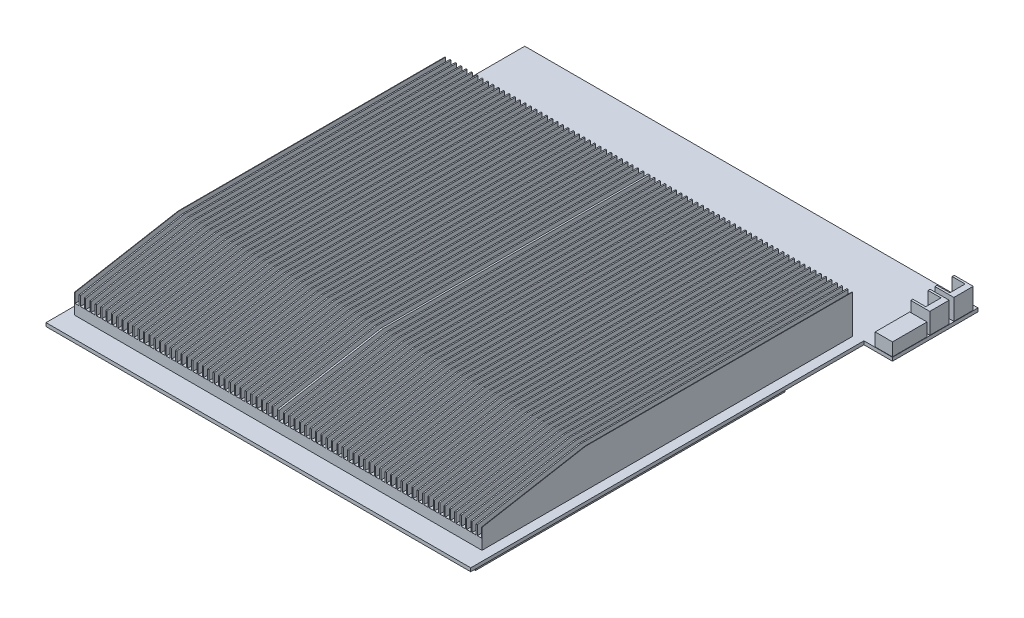
SolidWorks part; units mm, degrees
ref_plane "Front Plane" through (0, 0, 0) normal (0, 0, 1) x (1, 0, 0)
ref_plane "Top Plane" through (0, 0, 0) normal (0, 1, 0) x (1, 0, 0)
ref_plane "Right Plane" through (0, 0, 0) normal (1, 0, 0) x (0, 0, -1)
sketch "Sketch1" plane through (0, 0, 0) normal (0, 1, 0) x (1, 0, 0)
  line L0 (0, 0) -> (0, 277)
  line L1 (0, 277) -> (262.25, 277)
  line L2 (262.25, 277) -> (262.25, 227.5)
  line L3 (262.25, 227.5) -> (245.75, 227.5)
  line L4 (245.75, 227.5) -> (245.75, 0)
  line L5 (245.75, 0) -> (0, 0)
  dimension "D1" = 277
  dimension "D2" = 245.75
  dimension "D3" = 49.5
  dimension "D4" = 16.5
extrude "Boss-Extrude1" add sketch "Sketch1" along normal blind 2
sketch "Sketch2" plane through (0, 2, 0) normal (0, 1, 0) x (1, 0, 0)
  line L0 (245.75, 0) -> (245.75, 227.5) construction
  line L1 (4.5, 226.5) -> (240.25, 226.5)
  line L2 (4.5, 226.5) -> (4.5, 12)
  line L3 (4.5, 12) -> (240.25, 12)
  line L4 (240.25, 226.5) -> (240.25, 12)
  line L5 (4.5, 226.5) -> (240.25, 12) construction
  line L6 (4.5, 12) -> (240.25, 226.5) construction
  line L7 (0, 0) -> (245.75, 0) construction
  line L8 (0, 277) -> (0, 0) construction
  line L9 (262.25, 277) -> (0, 277) construction
  point P4 (122.375, 119.25)
  dimension "D1" = 5.5
  dimension "D2" = 12
  dimension "D3" = 4.5
  dimension "D4" = 50.5
extrude "Boss-Extrude2" add sketch "Sketch2" along normal blind 22.2
sketch "Sketch3" plane through (240.25, 0, 0) normal (1, 0, 0) x (0, 0, -1)
  line L0 (12, 13.5) -> (72, 24.2)
  line L1 (12, 24.2) -> (12, 2) construction
  line L2 (12, 24.2) -> (226.5, 24.2) construction
  line L3 (72, 24.2) -> (12, 24.2)
  line L4 (12, 24.2) -> (12, 13.5)
  dimension "D1" = 60
  dimension "D2" = 10.7
extrude "Cut-Extrude1" cut sketch "Sketch3" against normal up to surface (235.75 mm away) up to face at (4.5, 13.1, -119.25)
sketch "Sketch5" plane through (0, 0, 0) normal (0, -1, 0) x (1, 0, 0)
  line L0 (7.9691, -193.75) -> (7.9691, -14.75)
  line L6 (233.7585, -14.75) -> (233.7585, -193.75)
  line L9 (7.9691, -193.75) -> (67.4691, -193.75)
  line L10 (67.4691, -193.75) -> (67.4691, -226.5)
  line L11 (67.4691, -226.5) -> (174.2585, -226.5)
  line L12 (174.2585, -226.5) -> (174.2585, -193.75)
  line L13 (174.2585, -193.75) -> (233.7585, -193.75)
  line L14 (233.7585, -14.75) -> (7.9691, -14.75)
  line L15 (0, 0) -> (245.75, 0) construction
  line L16 (262.25, -277) -> (0, -277) construction
  line L18 (122.5508, -241.25) -> (149.8508, -241.25)
  line L19 (122.5508, -241.25) -> (122.5508, -271.5)
  line L20 (122.5508, -271.5) -> (149.8508, -271.5)
  line L21 (149.8508, -241.25) -> (149.8508, -271.5)
  line L22 (122.5508, -241.25) -> (149.8508, -271.5) construction
  line L23 (122.5508, -271.5) -> (149.8508, -241.25) construction
  point P16 (136.2008, -256.375)
  dimension "D1" = 14.75
  dimension "D2" = 50.5
  dimension "D3" = 83.25
  dimension "D4" = 59.5
  dimension "D5" = 5.5
  dimension "D6" = 14.75
  dimension "D7" = 27.3
extrude "Boss-Extrude4" add sketch "Sketch5" along normal blind 12.75
sketch "Sketch6" plane through (0, 0, -226.5) normal (0, 0, -1) x (-1, 0, 0)
  line L0 (-122.375, 24.2) -> (-122.375, 2) construction
  line L1 (-240.25, 24.2) -> (-4.5, 24.2) construction
  line L2 (-240.25, 2) -> (-4.5, 2) construction
  line L3 (-262.25, 2) -> (0, 2) construction
  line L4 (-122.875, 24.2) -> (-125.275, 24.2)
  line L5 (-122.875, 24.2) -> (-122.875, 8)
  line L6 (-122.875, 8) -> (-125.275, 8)
  line L7 (-125.275, 24.2) -> (-125.275, 8)
  line L8 (-122.875, 24.2) -> (-125.275, 8) construction
  line L9 (-122.875, 8) -> (-125.275, 24.2) construction
  line L10 (-121.875, 8) -> (-119.475, 24.2) construction
  line L11 (-121.875, 24.2) -> (-119.475, 8) construction
  line L12 (-119.475, 24.2) -> (-119.475, 8)
  line L13 (-121.875, 8) -> (-119.475, 8)
  line L14 (-121.875, 24.2) -> (-121.875, 8)
  line L15 (-121.875, 24.2) -> (-119.475, 24.2)
  line L16 (-125.975, 24.2) -> (-128.375, 24.2)
  line L17 (-125.975, 24.2) -> (-125.975, 8)
  line L18 (-125.975, 8) -> (-128.375, 8)
  line L19 (-128.375, 24.2) -> (-128.375, 8)
  line L20 (-125.975, 24.2) -> (-128.375, 8) construction
  line L21 (-125.975, 8) -> (-128.375, 24.2) construction
  line L22 (-129.075, 24.2) -> (-131.475, 24.2)
  line L23 (-129.075, 24.2) -> (-129.075, 8)
  line L24 (-129.075, 8) -> (-131.475, 8)
  line L25 (-131.475, 24.2) -> (-131.475, 8)
  line L26 (-129.075, 24.2) -> (-131.475, 8) construction
  line L27 (-129.075, 8) -> (-131.475, 24.2) construction
  line L28 (-132.175, 24.2) -> (-134.575, 24.2)
  line L29 (-132.175, 24.2) -> (-132.175, 8)
  line L30 (-132.175, 8) -> (-134.575, 8)
  line L31 (-134.575, 24.2) -> (-134.575, 8)
  line L32 (-132.175, 24.2) -> (-134.575, 8) construction
  line L33 (-132.175, 8) -> (-134.575, 24.2) construction
  line L34 (-135.275, 24.2) -> (-137.675, 24.2)
  line L35 (-135.275, 24.2) -> (-135.275, 8)
  line L36 (-135.275, 8) -> (-137.675, 8)
  line L37 (-137.675, 24.2) -> (-137.675, 8)
  line L38 (-135.275, 24.2) -> (-137.675, 8) construction
  line L39 (-135.275, 8) -> (-137.675, 24.2) construction
  line L40 (-138.375, 24.2) -> (-140.775, 24.2)
  line L41 (-138.375, 24.2) -> (-138.375, 8)
  line L42 (-138.375, 8) -> (-140.775, 8)
  line L43 (-140.775, 24.2) -> (-140.775, 8)
  line L44 (-138.375, 24.2) -> (-140.775, 8) construction
  line L45 (-138.375, 8) -> (-140.775, 24.2) construction
  line L46 (-141.475, 24.2) -> (-143.875, 24.2)
  line L47 (-141.475, 24.2) -> (-141.475, 8)
  line L48 (-141.475, 8) -> (-143.875, 8)
  line L49 (-143.875, 24.2) -> (-143.875, 8)
  line L50 (-141.475, 24.2) -> (-143.875, 8) construction
  line L51 (-141.475, 8) -> (-143.875, 24.2) construction
  line L52 (-144.575, 24.2) -> (-146.975, 24.2)
  line L53 (-144.575, 24.2) -> (-144.575, 8)
  line L54 (-144.575, 8) -> (-146.975, 8)
  line L55 (-146.975, 24.2) -> (-146.975, 8)
  line L56 (-144.575, 24.2) -> (-146.975, 8) construction
  line L57 (-144.575, 8) -> (-146.975, 24.2) construction
  line L58 (-147.675, 24.2) -> (-150.075, 24.2)
  line L59 (-147.675, 24.2) -> (-147.675, 8)
  line L60 (-147.675, 8) -> (-150.075, 8)
  line L61 (-150.075, 24.2) -> (-150.075, 8)
  line L62 (-147.675, 24.2) -> (-150.075, 8) construction
  line L63 (-147.675, 8) -> (-150.075, 24.2) construction
  line L64 (-150.775, 24.2) -> (-153.175, 24.2)
  line L65 (-150.775, 24.2) -> (-150.775, 8)
  line L66 (-150.775, 8) -> (-153.175, 8)
  line L67 (-153.175, 24.2) -> (-153.175, 8)
  line L68 (-150.775, 24.2) -> (-153.175, 8) construction
  line L69 (-150.775, 8) -> (-153.175, 24.2) construction
  line L70 (-153.875, 24.2) -> (-156.275, 24.2)
  line L71 (-153.875, 24.2) -> (-153.875, 8)
  line L72 (-153.875, 8) -> (-156.275, 8)
  line L73 (-156.275, 24.2) -> (-156.275, 8)
  line L74 (-153.875, 24.2) -> (-156.275, 8) construction
  line L75 (-153.875, 8) -> (-156.275, 24.2) construction
  line L76 (-156.975, 24.2) -> (-159.375, 24.2)
  line L77 (-156.975, 24.2) -> (-156.975, 8)
  line L78 (-156.975, 8) -> (-159.375, 8)
  line L79 (-159.375, 24.2) -> (-159.375, 8)
  line L80 (-156.975, 24.2) -> (-159.375, 8) construction
  line L81 (-156.975, 8) -> (-159.375, 24.2) construction
  line L82 (-160.075, 24.2) -> (-162.475, 24.2)
  line L83 (-160.075, 24.2) -> (-160.075, 8)
  line L84 (-160.075, 8) -> (-162.475, 8)
  line L85 (-162.475, 24.2) -> (-162.475, 8)
  line L86 (-160.075, 24.2) -> (-162.475, 8) construction
  line L87 (-160.075, 8) -> (-162.475, 24.2) construction
  line L88 (-163.175, 24.2) -> (-165.575, 24.2)
  line L89 (-163.175, 24.2) -> (-163.175, 8)
  line L90 (-163.175, 8) -> (-165.575, 8)
  line L91 (-165.575, 24.2) -> (-165.575, 8)
  line L92 (-163.175, 24.2) -> (-165.575, 8) construction
  line L93 (-163.175, 8) -> (-165.575, 24.2) construction
  line L94 (-166.275, 24.2) -> (-168.675, 24.2)
  line L95 (-166.275, 24.2) -> (-166.275, 8)
  line L96 (-166.275, 8) -> (-168.675, 8)
  line L97 (-168.675, 24.2) -> (-168.675, 8)
  line L98 (-166.275, 24.2) -> (-168.675, 8) construction
  line L99 (-166.275, 8) -> (-168.675, 24.2) construction
  line L100 (-169.375, 24.2) -> (-171.775, 24.2)
  line L101 (-169.375, 24.2) -> (-169.375, 8)
  line L102 (-169.375, 8) -> (-171.775, 8)
  line L103 (-171.775, 24.2) -> (-171.775, 8)
  line L104 (-169.375, 24.2) -> (-171.775, 8) construction
  line L105 (-169.375, 8) -> (-171.775, 24.2) construction
  line L106 (-172.475, 24.2) -> (-174.875, 24.2)
  line L107 (-172.475, 24.2) -> (-172.475, 8)
  line L108 (-172.475, 8) -> (-174.875, 8)
  line L109 (-174.875, 24.2) -> (-174.875, 8)
  line L110 (-172.475, 24.2) -> (-174.875, 8) construction
  line L111 (-172.475, 8) -> (-174.875, 24.2) construction
  line L112 (-175.575, 24.2) -> (-177.975, 24.2)
  line L113 (-175.575, 24.2) -> (-175.575, 8)
  line L114 (-175.575, 8) -> (-177.975, 8)
  line L115 (-177.975, 24.2) -> (-177.975, 8)
  line L116 (-175.575, 24.2) -> (-177.975, 8) construction
  line L117 (-175.575, 8) -> (-177.975, 24.2) construction
  line L118 (-178.675, 24.2) -> (-181.075, 24.2)
  line L119 (-178.675, 24.2) -> (-178.675, 8)
  line L120 (-178.675, 8) -> (-181.075, 8)
  line L121 (-181.075, 24.2) -> (-181.075, 8)
  line L122 (-178.675, 24.2) -> (-181.075, 8) construction
  line L123 (-178.675, 8) -> (-181.075, 24.2) construction
  line L124 (-181.775, 24.2) -> (-184.175, 24.2)
  line L125 (-181.775, 24.2) -> (-181.775, 8)
  line L126 (-181.775, 8) -> (-184.175, 8)
  line L127 (-184.175, 24.2) -> (-184.175, 8)
  line L128 (-181.775, 24.2) -> (-184.175, 8) construction
  line L129 (-181.775, 8) -> (-184.175, 24.2) construction
  line L130 (-184.875, 24.2) -> (-187.275, 24.2)
  line L131 (-184.875, 24.2) -> (-184.875, 8)
  line L132 (-184.875, 8) -> (-187.275, 8)
  line L133 (-187.275, 24.2) -> (-187.275, 8)
  line L134 (-184.875, 24.2) -> (-187.275, 8) construction
  line L135 (-184.875, 8) -> (-187.275, 24.2) construction
  line L136 (-187.975, 24.2) -> (-190.375, 24.2)
  line L137 (-187.975, 24.2) -> (-187.975, 8)
  line L138 (-187.975, 8) -> (-190.375, 8)
  line L139 (-190.375, 24.2) -> (-190.375, 8)
  line L140 (-187.975, 24.2) -> (-190.375, 8) construction
  line L141 (-187.975, 8) -> (-190.375, 24.2) construction
  line L142 (-191.075, 24.2) -> (-193.475, 24.2)
  line L143 (-191.075, 24.2) -> (-191.075, 8)
  line L144 (-191.075, 8) -> (-193.475, 8)
  line L145 (-193.475, 24.2) -> (-193.475, 8)
  line L146 (-191.075, 24.2) -> (-193.475, 8) construction
  line L147 (-191.075, 8) -> (-193.475, 24.2) construction
  line L148 (-194.175, 24.2) -> (-196.575, 24.2)
  line L149 (-194.175, 24.2) -> (-194.175, 8)
  line L150 (-194.175, 8) -> (-196.575, 8)
  line L151 (-196.575, 24.2) -> (-196.575, 8)
  line L152 (-194.175, 24.2) -> (-196.575, 8) construction
  line L153 (-194.175, 8) -> (-196.575, 24.2) construction
  line L154 (-197.275, 24.2) -> (-199.675, 24.2)
  line L155 (-197.275, 24.2) -> (-197.275, 8)
  line L156 (-197.275, 8) -> (-199.675, 8)
  line L157 (-199.675, 24.2) -> (-199.675, 8)
  line L158 (-197.275, 24.2) -> (-199.675, 8) construction
  line L159 (-197.275, 8) -> (-199.675, 24.2) construction
  line L160 (-200.375, 24.2) -> (-202.775, 24.2)
  line L161 (-200.375, 24.2) -> (-200.375, 8)
  line L162 (-200.375, 8) -> (-202.775, 8)
  line L163 (-202.775, 24.2) -> (-202.775, 8)
  line L164 (-200.375, 24.2) -> (-202.775, 8) construction
  line L165 (-200.375, 8) -> (-202.775, 24.2) construction
  line L166 (-203.475, 24.2) -> (-205.875, 24.2)
  line L167 (-203.475, 24.2) -> (-203.475, 8)
  line L168 (-203.475, 8) -> (-205.875, 8)
  line L169 (-205.875, 24.2) -> (-205.875, 8)
  line L170 (-203.475, 24.2) -> (-205.875, 8) construction
  line L171 (-203.475, 8) -> (-205.875, 24.2) construction
  line L172 (-206.575, 24.2) -> (-208.975, 24.2)
  line L173 (-206.575, 24.2) -> (-206.575, 8)
  line L174 (-206.575, 8) -> (-208.975, 8)
  line L175 (-208.975, 24.2) -> (-208.975, 8)
  line L176 (-206.575, 24.2) -> (-208.975, 8) construction
  line L177 (-206.575, 8) -> (-208.975, 24.2) construction
  line L178 (-209.675, 24.2) -> (-212.075, 24.2)
  line L179 (-209.675, 24.2) -> (-209.675, 8)
  line L180 (-209.675, 8) -> (-212.075, 8)
  line L181 (-212.075, 24.2) -> (-212.075, 8)
  line L182 (-209.675, 24.2) -> (-212.075, 8) construction
  line L183 (-209.675, 8) -> (-212.075, 24.2) construction
  line L184 (-212.775, 24.2) -> (-215.175, 24.2)
  line L185 (-212.775, 24.2) -> (-212.775, 8)
  line L186 (-212.775, 8) -> (-215.175, 8)
  line L187 (-215.175, 24.2) -> (-215.175, 8)
  line L188 (-212.775, 24.2) -> (-215.175, 8) construction
  line L189 (-212.775, 8) -> (-215.175, 24.2) construction
  line L190 (-215.875, 24.2) -> (-218.275, 24.2)
  line L191 (-215.875, 24.2) -> (-215.875, 8)
  line L192 (-215.875, 8) -> (-218.275, 8)
  line L193 (-218.275, 24.2) -> (-218.275, 8)
  line L194 (-215.875, 24.2) -> (-218.275, 8) construction
  line L195 (-215.875, 8) -> (-218.275, 24.2) construction
  line L196 (-218.975, 24.2) -> (-221.375, 24.2)
  line L197 (-218.975, 24.2) -> (-218.975, 8)
  line L198 (-218.975, 8) -> (-221.375, 8)
  line L199 (-221.375, 24.2) -> (-221.375, 8)
  line L200 (-218.975, 24.2) -> (-221.375, 8) construction
  line L201 (-218.975, 8) -> (-221.375, 24.2) construction
  line L202 (-222.075, 24.2) -> (-224.475, 24.2)
  line L203 (-222.075, 24.2) -> (-222.075, 8)
  line L204 (-222.075, 8) -> (-224.475, 8)
  line L205 (-224.475, 24.2) -> (-224.475, 8)
  line L206 (-222.075, 24.2) -> (-224.475, 8) construction
  line L207 (-222.075, 8) -> (-224.475, 24.2) construction
  line L208 (-225.175, 24.2) -> (-227.575, 24.2)
  line L209 (-225.175, 24.2) -> (-225.175, 8)
  line L210 (-225.175, 8) -> (-227.575, 8)
  line L211 (-227.575, 24.2) -> (-227.575, 8)
  line L212 (-225.175, 24.2) -> (-227.575, 8) construction
  line L213 (-225.175, 8) -> (-227.575, 24.2) construction
  line L214 (-228.275, 24.2) -> (-230.675, 24.2)
  line L215 (-228.275, 24.2) -> (-228.275, 8)
  line L216 (-228.275, 8) -> (-230.675, 8)
  line L217 (-230.675, 24.2) -> (-230.675, 8)
  line L218 (-228.275, 24.2) -> (-230.675, 8) construction
  line L219 (-228.275, 8) -> (-230.675, 24.2) construction
  line L220 (-231.375, 24.2) -> (-233.775, 24.2)
  line L221 (-231.375, 24.2) -> (-231.375, 8)
  line L222 (-231.375, 8) -> (-233.775, 8)
  line L223 (-233.775, 24.2) -> (-233.775, 8)
  line L224 (-231.375, 24.2) -> (-233.775, 8) construction
  line L225 (-231.375, 8) -> (-233.775, 24.2) construction
  line L226 (-234.475, 24.2) -> (-236.875, 24.2)
  line L227 (-234.475, 24.2) -> (-234.475, 8)
  line L228 (-234.475, 8) -> (-236.875, 8)
  line L229 (-236.875, 24.2) -> (-236.875, 8)
  line L230 (-234.475, 24.2) -> (-236.875, 8) construction
  line L231 (-234.475, 8) -> (-236.875, 24.2) construction
  line L232 (-237.575, 24.2) -> (-239.975, 24.2)
  line L233 (-237.575, 24.2) -> (-237.575, 8)
  line L234 (-237.575, 8) -> (-239.975, 8)
  line L235 (-239.975, 24.2) -> (-239.975, 8)
  line L236 (-237.575, 24.2) -> (-239.975, 8) construction
  line L237 (-237.575, 8) -> (-239.975, 24.2) construction
  line L238 (-116.375, 24.2) -> (-116.375, 8)
  line L239 (-118.775, 8) -> (-116.375, 8)
  line L240 (-118.775, 24.2) -> (-118.775, 8)
  line L241 (-118.775, 24.2) -> (-116.375, 24.2)
  line L242 (-118.775, 8) -> (-116.375, 24.2) construction
  line L243 (-118.775, 24.2) -> (-116.375, 8) construction
  line L244 (-113.275, 24.2) -> (-113.275, 8)
  line L245 (-115.675, 8) -> (-113.275, 8)
  line L246 (-115.675, 24.2) -> (-115.675, 8)
  line L247 (-115.675, 24.2) -> (-113.275, 24.2)
  line L248 (-115.675, 8) -> (-113.275, 24.2) construction
  line L249 (-115.675, 24.2) -> (-113.275, 8) construction
  line L250 (-110.175, 24.2) -> (-110.175, 8)
  line L251 (-112.575, 8) -> (-110.175, 8)
  line L252 (-112.575, 24.2) -> (-112.575, 8)
  line L253 (-112.575, 24.2) -> (-110.175, 24.2)
  line L254 (-112.575, 8) -> (-110.175, 24.2) construction
  line L255 (-112.575, 24.2) -> (-110.175, 8) construction
  line L256 (-107.075, 24.2) -> (-107.075, 8)
  line L257 (-109.475, 8) -> (-107.075, 8)
  line L258 (-109.475, 24.2) -> (-109.475, 8)
  line L259 (-109.475, 24.2) -> (-107.075, 24.2)
  line L260 (-109.475, 8) -> (-107.075, 24.2) construction
  line L261 (-109.475, 24.2) -> (-107.075, 8) construction
  line L262 (-103.975, 24.2) -> (-103.975, 8)
  line L263 (-106.375, 8) -> (-103.975, 8)
  line L264 (-106.375, 24.2) -> (-106.375, 8)
  line L265 (-106.375, 24.2) -> (-103.975, 24.2)
  line L266 (-106.375, 8) -> (-103.975, 24.2) construction
  line L267 (-106.375, 24.2) -> (-103.975, 8) construction
  line L268 (-100.875, 24.2) -> (-100.875, 8)
  line L269 (-103.275, 8) -> (-100.875, 8)
  line L270 (-103.275, 24.2) -> (-103.275, 8)
  line L271 (-103.275, 24.2) -> (-100.875, 24.2)
  line L272 (-103.275, 8) -> (-100.875, 24.2) construction
  line L273 (-103.275, 24.2) -> (-100.875, 8) construction
  line L274 (-97.775, 24.2) -> (-97.775, 8)
  line L275 (-100.175, 8) -> (-97.775, 8)
  line L276 (-100.175, 24.2) -> (-100.175, 8)
  line L277 (-100.175, 24.2) -> (-97.775, 24.2)
  line L278 (-100.175, 8) -> (-97.775, 24.2) construction
  line L279 (-100.175, 24.2) -> (-97.775, 8) construction
  line L280 (-94.675, 24.2) -> (-94.675, 8)
  line L281 (-97.075, 8) -> (-94.675, 8)
  line L282 (-97.075, 24.2) -> (-97.075, 8)
  line L283 (-97.075, 24.2) -> (-94.675, 24.2)
  line L284 (-97.075, 8) -> (-94.675, 24.2) construction
  line L285 (-97.075, 24.2) -> (-94.675, 8) construction
  line L286 (-91.575, 24.2) -> (-91.575, 8)
  line L287 (-93.975, 8) -> (-91.575, 8)
  line L288 (-93.975, 24.2) -> (-93.975, 8)
  line L289 (-93.975, 24.2) -> (-91.575, 24.2)
  line L290 (-93.975, 8) -> (-91.575, 24.2) construction
  line L291 (-93.975, 24.2) -> (-91.575, 8) construction
  line L292 (-88.475, 24.2) -> (-88.475, 8)
  line L293 (-90.875, 8) -> (-88.475, 8)
  line L294 (-90.875, 24.2) -> (-90.875, 8)
  line L295 (-90.875, 24.2) -> (-88.475, 24.2)
  line L296 (-90.875, 8) -> (-88.475, 24.2) construction
  line L297 (-90.875, 24.2) -> (-88.475, 8) construction
  line L298 (-85.375, 24.2) -> (-85.375, 8)
  line L299 (-87.775, 8) -> (-85.375, 8)
  line L300 (-87.775, 24.2) -> (-87.775, 8)
  line L301 (-87.775, 24.2) -> (-85.375, 24.2)
  line L302 (-87.775, 8) -> (-85.375, 24.2) construction
  line L303 (-87.775, 24.2) -> (-85.375, 8) construction
  line L304 (-82.275, 24.2) -> (-82.275, 8)
  line L305 (-84.675, 8) -> (-82.275, 8)
  line L306 (-84.675, 24.2) -> (-84.675, 8)
  line L307 (-84.675, 24.2) -> (-82.275, 24.2)
  line L308 (-84.675, 8) -> (-82.275, 24.2) construction
  line L309 (-84.675, 24.2) -> (-82.275, 8) construction
  line L310 (-79.175, 24.2) -> (-79.175, 8)
  line L311 (-81.575, 8) -> (-79.175, 8)
  line L312 (-81.575, 24.2) -> (-81.575, 8)
  line L313 (-81.575, 24.2) -> (-79.175, 24.2)
  line L314 (-81.575, 8) -> (-79.175, 24.2) construction
  line L315 (-81.575, 24.2) -> (-79.175, 8) construction
  line L316 (-76.075, 24.2) -> (-76.075, 8)
  line L317 (-78.475, 8) -> (-76.075, 8)
  line L318 (-78.475, 24.2) -> (-78.475, 8)
  line L319 (-78.475, 24.2) -> (-76.075, 24.2)
  line L320 (-78.475, 8) -> (-76.075, 24.2) construction
  line L321 (-78.475, 24.2) -> (-76.075, 8) construction
  line L322 (-72.975, 24.2) -> (-72.975, 8)
  line L323 (-75.375, 8) -> (-72.975, 8)
  line L324 (-75.375, 24.2) -> (-75.375, 8)
  line L325 (-75.375, 24.2) -> (-72.975, 24.2)
  line L326 (-75.375, 8) -> (-72.975, 24.2) construction
  line L327 (-75.375, 24.2) -> (-72.975, 8) construction
  line L328 (-69.875, 24.2) -> (-69.875, 8)
  line L329 (-72.275, 8) -> (-69.875, 8)
  line L330 (-72.275, 24.2) -> (-72.275, 8)
  line L331 (-72.275, 24.2) -> (-69.875, 24.2)
  line L332 (-72.275, 8) -> (-69.875, 24.2) construction
  line L333 (-72.275, 24.2) -> (-69.875, 8) construction
  line L334 (-66.775, 24.2) -> (-66.775, 8)
  line L335 (-69.175, 8) -> (-66.775, 8)
  line L336 (-69.175, 24.2) -> (-69.175, 8)
  line L337 (-69.175, 24.2) -> (-66.775, 24.2)
  line L338 (-69.175, 8) -> (-66.775, 24.2) construction
  line L339 (-69.175, 24.2) -> (-66.775, 8) construction
  line L340 (-63.675, 24.2) -> (-63.675, 8)
  line L341 (-66.075, 8) -> (-63.675, 8)
  line L342 (-66.075, 24.2) -> (-66.075, 8)
  line L343 (-66.075, 24.2) -> (-63.675, 24.2)
  line L344 (-66.075, 8) -> (-63.675, 24.2) construction
  line L345 (-66.075, 24.2) -> (-63.675, 8) construction
  line L346 (-60.575, 24.2) -> (-60.575, 8)
  line L347 (-62.975, 8) -> (-60.575, 8)
  line L348 (-62.975, 24.2) -> (-62.975, 8)
  line L349 (-62.975, 24.2) -> (-60.575, 24.2)
  line L350 (-62.975, 8) -> (-60.575, 24.2) construction
  line L351 (-62.975, 24.2) -> (-60.575, 8) construction
  line L352 (-57.475, 24.2) -> (-57.475, 8)
  line L353 (-59.875, 8) -> (-57.475, 8)
  line L354 (-59.875, 24.2) -> (-59.875, 8)
  line L355 (-59.875, 24.2) -> (-57.475, 24.2)
  line L356 (-59.875, 8) -> (-57.475, 24.2) construction
  line L357 (-59.875, 24.2) -> (-57.475, 8) construction
  line L358 (-54.375, 24.2) -> (-54.375, 8)
  line L359 (-56.775, 8) -> (-54.375, 8)
  line L360 (-56.775, 24.2) -> (-56.775, 8)
  line L361 (-56.775, 24.2) -> (-54.375, 24.2)
  line L362 (-56.775, 8) -> (-54.375, 24.2) construction
  line L363 (-56.775, 24.2) -> (-54.375, 8) construction
  line L364 (-51.275, 24.2) -> (-51.275, 8)
  line L365 (-53.675, 8) -> (-51.275, 8)
  line L366 (-53.675, 24.2) -> (-53.675, 8)
  line L367 (-53.675, 24.2) -> (-51.275, 24.2)
  line L368 (-53.675, 8) -> (-51.275, 24.2) construction
  line L369 (-53.675, 24.2) -> (-51.275, 8) construction
  line L370 (-48.175, 24.2) -> (-48.175, 8)
  line L371 (-50.575, 8) -> (-48.175, 8)
  line L372 (-50.575, 24.2) -> (-50.575, 8)
  line L373 (-50.575, 24.2) -> (-48.175, 24.2)
  line L374 (-50.575, 8) -> (-48.175, 24.2) construction
  line L375 (-50.575, 24.2) -> (-48.175, 8) construction
  line L376 (-45.075, 24.2) -> (-45.075, 8)
  line L377 (-47.475, 8) -> (-45.075, 8)
  line L378 (-47.475, 24.2) -> (-47.475, 8)
  line L379 (-47.475, 24.2) -> (-45.075, 24.2)
  line L380 (-47.475, 8) -> (-45.075, 24.2) construction
  line L381 (-47.475, 24.2) -> (-45.075, 8) construction
  line L382 (-41.975, 24.2) -> (-41.975, 8)
  line L383 (-44.375, 8) -> (-41.975, 8)
  line L384 (-44.375, 24.2) -> (-44.375, 8)
  line L385 (-44.375, 24.2) -> (-41.975, 24.2)
  line L386 (-44.375, 8) -> (-41.975, 24.2) construction
  line L387 (-44.375, 24.2) -> (-41.975, 8) construction
  line L388 (-38.875, 24.2) -> (-38.875, 8)
  line L389 (-41.275, 8) -> (-38.875, 8)
  line L390 (-41.275, 24.2) -> (-41.275, 8)
  line L391 (-41.275, 24.2) -> (-38.875, 24.2)
  line L392 (-41.275, 8) -> (-38.875, 24.2) construction
  line L393 (-41.275, 24.2) -> (-38.875, 8) construction
  line L394 (-35.775, 24.2) -> (-35.775, 8)
  line L395 (-38.175, 8) -> (-35.775, 8)
  line L396 (-38.175, 24.2) -> (-38.175, 8)
  line L397 (-38.175, 24.2) -> (-35.775, 24.2)
  line L398 (-38.175, 8) -> (-35.775, 24.2) construction
  line L399 (-38.175, 24.2) -> (-35.775, 8) construction
  line L400 (-32.675, 24.2) -> (-32.675, 8)
  line L401 (-35.075, 8) -> (-32.675, 8)
  line L402 (-35.075, 24.2) -> (-35.075, 8)
  line L403 (-35.075, 24.2) -> (-32.675, 24.2)
  line L404 (-35.075, 8) -> (-32.675, 24.2) construction
  line L405 (-35.075, 24.2) -> (-32.675, 8) construction
  line L406 (-29.575, 24.2) -> (-29.575, 8)
  line L407 (-31.975, 8) -> (-29.575, 8)
  line L408 (-31.975, 24.2) -> (-31.975, 8)
  line L409 (-31.975, 24.2) -> (-29.575, 24.2)
  line L410 (-31.975, 8) -> (-29.575, 24.2) construction
  line L411 (-31.975, 24.2) -> (-29.575, 8) construction
  line L412 (-26.475, 24.2) -> (-26.475, 8)
  line L413 (-28.875, 8) -> (-26.475, 8)
  line L414 (-28.875, 24.2) -> (-28.875, 8)
  line L415 (-28.875, 24.2) -> (-26.475, 24.2)
  line L416 (-28.875, 8) -> (-26.475, 24.2) construction
  line L417 (-28.875, 24.2) -> (-26.475, 8) construction
  line L418 (-23.375, 24.2) -> (-23.375, 8)
  line L419 (-25.775, 8) -> (-23.375, 8)
  line L420 (-25.775, 24.2) -> (-25.775, 8)
  line L421 (-25.775, 24.2) -> (-23.375, 24.2)
  line L422 (-25.775, 8) -> (-23.375, 24.2) construction
  line L423 (-25.775, 24.2) -> (-23.375, 8) construction
  line L424 (-20.275, 24.2) -> (-20.275, 8)
  line L425 (-22.675, 8) -> (-20.275, 8)
  line L426 (-22.675, 24.2) -> (-22.675, 8)
  line L427 (-22.675, 24.2) -> (-20.275, 24.2)
  line L428 (-22.675, 8) -> (-20.275, 24.2) construction
  line L429 (-22.675, 24.2) -> (-20.275, 8) construction
  line L430 (-17.175, 24.2) -> (-17.175, 8)
  line L431 (-19.575, 8) -> (-17.175, 8)
  line L432 (-19.575, 24.2) -> (-19.575, 8)
  line L433 (-19.575, 24.2) -> (-17.175, 24.2)
  line L434 (-19.575, 8) -> (-17.175, 24.2) construction
  line L435 (-19.575, 24.2) -> (-17.175, 8) construction
  line L436 (-14.075, 24.2) -> (-14.075, 8)
  line L437 (-16.475, 8) -> (-14.075, 8)
  line L438 (-16.475, 24.2) -> (-16.475, 8)
  line L439 (-16.475, 24.2) -> (-14.075, 24.2)
  line L440 (-16.475, 8) -> (-14.075, 24.2) construction
  line L441 (-16.475, 24.2) -> (-14.075, 8) construction
  line L442 (-10.975, 24.2) -> (-10.975, 8)
  line L443 (-13.375, 8) -> (-10.975, 8)
  line L444 (-13.375, 24.2) -> (-13.375, 8)
  line L445 (-13.375, 24.2) -> (-10.975, 24.2)
  line L446 (-13.375, 8) -> (-10.975, 24.2) construction
  line L447 (-13.375, 24.2) -> (-10.975, 8) construction
  line L448 (-7.875, 24.2) -> (-7.875, 8)
  line L449 (-10.275, 8) -> (-7.875, 8)
  line L450 (-10.275, 24.2) -> (-10.275, 8)
  line L451 (-10.275, 24.2) -> (-7.875, 24.2)
  line L452 (-10.275, 8) -> (-7.875, 24.2) construction
  line L453 (-10.275, 24.2) -> (-7.875, 8) construction
  line L454 (-4.775, 24.2) -> (-4.775, 8)
  line L455 (-7.175, 8) -> (-4.775, 8)
  line L456 (-7.175, 24.2) -> (-7.175, 8)
  line L457 (-7.175, 24.2) -> (-4.775, 24.2)
  line L458 (-7.175, 8) -> (-4.775, 24.2) construction
  line L459 (-7.175, 24.2) -> (-4.775, 8) construction
  point P10 (-124.075, 16.1)
  point P17 (-120.675, 16.1)
  point P23 (-127.175, 16.1)
  point P28 (-130.275, 16.1)
  point P33 (-133.375, 16.1)
  point P38 (-136.475, 16.1)
  point P43 (-139.575, 16.1)
  point P48 (-142.675, 16.1)
  point P53 (-145.775, 16.1)
  point P58 (-148.875, 16.1)
  point P63 (-151.975, 16.1)
  point P68 (-155.075, 16.1)
  point P73 (-158.175, 16.1)
  point P78 (-161.275, 16.1)
  point P83 (-164.375, 16.1)
  point P88 (-167.475, 16.1)
  point P93 (-170.575, 16.1)
  point P98 (-173.675, 16.1)
  point P103 (-176.775, 16.1)
  point P108 (-179.875, 16.1)
  point P113 (-182.975, 16.1)
  point P118 (-186.075, 16.1)
  point P123 (-189.175, 16.1)
  point P128 (-192.275, 16.1)
  point P133 (-195.375, 16.1)
  point P138 (-198.475, 16.1)
  point P143 (-201.575, 16.1)
  point P148 (-204.675, 16.1)
  point P153 (-207.775, 16.1)
  point P158 (-210.875, 16.1)
  point P163 (-213.975, 16.1)
  point P168 (-217.075, 16.1)
  point P173 (-220.175, 16.1)
  point P178 (-223.275, 16.1)
  point P183 (-226.375, 16.1)
  point P188 (-229.475, 16.1)
  point P193 (-232.575, 16.1)
  point P198 (-235.675, 16.1)
  point P203 (-238.775, 16.1)
  point P209 (-117.575, 16.1)
  point P214 (-114.475, 16.1)
  point P219 (-111.375, 16.1)
  point P224 (-108.275, 16.1)
  point P229 (-105.175, 16.1)
  point P234 (-102.075, 16.1)
  point P239 (-98.975, 16.1)
  point P244 (-95.875, 16.1)
  point P249 (-92.775, 16.1)
  point P254 (-89.675, 16.1)
  point P259 (-86.575, 16.1)
  point P264 (-83.475, 16.1)
  point P269 (-80.375, 16.1)
  point P274 (-77.275, 16.1)
  point P279 (-74.175, 16.1)
  point P284 (-71.075, 16.1)
  point P289 (-67.975, 16.1)
  point P294 (-64.875, 16.1)
  point P299 (-61.775, 16.1)
  point P304 (-58.675, 16.1)
  point P309 (-55.575, 16.1)
  point P314 (-52.475, 16.1)
  point P319 (-49.375, 16.1)
  point P324 (-46.275, 16.1)
  point P329 (-43.175, 16.1)
  point P334 (-40.075, 16.1)
  point P339 (-36.975, 16.1)
  point P344 (-33.875, 16.1)
  point P349 (-30.775, 16.1)
  point P354 (-27.675, 16.1)
  point P359 (-24.575, 16.1)
  point P364 (-21.475, 16.1)
  point P369 (-18.375, 16.1)
  point P374 (-15.275, 16.1)
  point P379 (-12.175, 16.1)
  point P384 (-9.075, 16.1)
  point P389 (-5.975, 16.1)
  dimension "D1" = 1
  dimension "D2" = 6
  dimension "D3" = 2.4
  dimension "D4" = 38
  dimension "D5" = 38
extrude "Cut-Extrude2" cut sketch "Sketch6" against normal through all
sketch "Sketch7" plane through (0, 0, -14.75) normal (0, 0, 1) x (1, 0, 0)
  line L0 (120.8638, 0) -> (120.8638, -12.75) construction
  line L1 (233.7585, 0) -> (7.9691, 0) construction
  line L2 (233.7585, -12.75) -> (7.9691, -12.75) construction
  line L3 (121.8638, -1.9399) -> (124.2638, -12.75) construction
  line L4 (119.8638, -12.75) -> (117.4638, -12.75)
  line L5 (119.8638, -12.75) -> (119.8638, -1.9399)
  line L6 (119.8638, -1.9399) -> (117.4638, -1.9399)
  line L7 (117.4638, -12.75) -> (117.4638, -1.9399)
  line L8 (119.8638, -12.75) -> (117.4638, -1.9399) construction
  line L9 (119.8638, -1.9399) -> (117.4638, -12.75) construction
  line L10 (121.8638, -12.75) -> (124.2638, -1.9399) construction
  line L11 (124.2638, -12.75) -> (124.2638, -1.9399)
  line L12 (121.8638, -1.9399) -> (124.2638, -1.9399)
  line L13 (121.8638, -12.75) -> (121.8638, -1.9399)
  line L14 (121.8638, -12.75) -> (124.2638, -12.75)
  line L15 (127.3638, -12.75) -> (127.3638, -1.9399)
  line L16 (124.9638, -1.9399) -> (127.3638, -1.9399)
  line L17 (124.9638, -12.75) -> (124.9638, -1.9399)
  line L18 (124.9638, -12.75) -> (127.3638, -12.75)
  line L19 (124.9638, -1.9399) -> (127.3638, -12.75) construction
  line L20 (124.9638, -12.75) -> (127.3638, -1.9399) construction
  line L21 (130.4638, -12.75) -> (130.4638, -1.9399)
  line L22 (128.0638, -1.9399) -> (130.4638, -1.9399)
  line L23 (128.0638, -12.75) -> (128.0638, -1.9399)
  line L24 (128.0638, -12.75) -> (130.4638, -12.75)
  line L25 (128.0638, -1.9399) -> (130.4638, -12.75) construction
  line L26 (128.0638, -12.75) -> (130.4638, -1.9399) construction
  line L27 (133.5638, -12.75) -> (133.5638, -1.9399)
  line L28 (131.1638, -1.9399) -> (133.5638, -1.9399)
  line L29 (131.1638, -12.75) -> (131.1638, -1.9399)
  line L30 (131.1638, -12.75) -> (133.5638, -12.75)
  line L31 (131.1638, -1.9399) -> (133.5638, -12.75) construction
  line L32 (131.1638, -12.75) -> (133.5638, -1.9399) construction
  line L33 (136.6638, -12.75) -> (136.6638, -1.9399)
  line L34 (134.2638, -1.9399) -> (136.6638, -1.9399)
  line L35 (134.2638, -12.75) -> (134.2638, -1.9399)
  line L36 (134.2638, -12.75) -> (136.6638, -12.75)
  line L37 (134.2638, -1.9399) -> (136.6638, -12.75) construction
  line L38 (134.2638, -12.75) -> (136.6638, -1.9399) construction
  line L39 (139.7638, -12.75) -> (139.7638, -1.9399)
  line L40 (137.3638, -1.9399) -> (139.7638, -1.9399)
  line L41 (137.3638, -12.75) -> (137.3638, -1.9399)
  line L42 (137.3638, -12.75) -> (139.7638, -12.75)
  line L43 (137.3638, -1.9399) -> (139.7638, -12.75) construction
  line L44 (137.3638, -12.75) -> (139.7638, -1.9399) construction
  line L45 (142.8638, -12.75) -> (142.8638, -1.9399)
  line L46 (140.4638, -1.9399) -> (142.8638, -1.9399)
  line L47 (140.4638, -12.75) -> (140.4638, -1.9399)
  line L48 (140.4638, -12.75) -> (142.8638, -12.75)
  line L49 (140.4638, -1.9399) -> (142.8638, -12.75) construction
  line L50 (140.4638, -12.75) -> (142.8638, -1.9399) construction
  line L51 (145.9638, -12.75) -> (145.9638, -1.9399)
  line L52 (143.5638, -1.9399) -> (145.9638, -1.9399)
  line L53 (143.5638, -12.75) -> (143.5638, -1.9399)
  line L54 (143.5638, -12.75) -> (145.9638, -12.75)
  line L55 (143.5638, -1.9399) -> (145.9638, -12.75) construction
  line L56 (143.5638, -12.75) -> (145.9638, -1.9399) construction
  line L57 (149.0638, -12.75) -> (149.0638, -1.9399)
  line L58 (146.6638, -1.9399) -> (149.0638, -1.9399)
  line L59 (146.6638, -12.75) -> (146.6638, -1.9399)
  line L60 (146.6638, -12.75) -> (149.0638, -12.75)
  line L61 (146.6638, -1.9399) -> (149.0638, -12.75) construction
  line L62 (146.6638, -12.75) -> (149.0638, -1.9399) construction
  line L63 (152.1638, -12.75) -> (152.1638, -1.9399)
  line L64 (149.7638, -1.9399) -> (152.1638, -1.9399)
  line L65 (149.7638, -12.75) -> (149.7638, -1.9399)
  line L66 (149.7638, -12.75) -> (152.1638, -12.75)
  line L67 (149.7638, -1.9399) -> (152.1638, -12.75) construction
  line L68 (149.7638, -12.75) -> (152.1638, -1.9399) construction
  line L69 (155.2638, -12.75) -> (155.2638, -1.9399)
  line L70 (152.8638, -1.9399) -> (155.2638, -1.9399)
  line L71 (152.8638, -12.75) -> (152.8638, -1.9399)
  line L72 (152.8638, -12.75) -> (155.2638, -12.75)
  line L73 (152.8638, -1.9399) -> (155.2638, -12.75) construction
  line L74 (152.8638, -12.75) -> (155.2638, -1.9399) construction
  line L75 (158.3638, -12.75) -> (158.3638, -1.9399)
  line L76 (155.9638, -1.9399) -> (158.3638, -1.9399)
  line L77 (155.9638, -12.75) -> (155.9638, -1.9399)
  line L78 (155.9638, -12.75) -> (158.3638, -12.75)
  line L79 (155.9638, -1.9399) -> (158.3638, -12.75) construction
  line L80 (155.9638, -12.75) -> (158.3638, -1.9399) construction
  line L81 (161.4638, -12.75) -> (161.4638, -1.9399)
  line L82 (159.0638, -1.9399) -> (161.4638, -1.9399)
  line L83 (159.0638, -12.75) -> (159.0638, -1.9399)
  line L84 (159.0638, -12.75) -> (161.4638, -12.75)
  line L85 (159.0638, -1.9399) -> (161.4638, -12.75) construction
  line L86 (159.0638, -12.75) -> (161.4638, -1.9399) construction
  line L87 (164.5638, -12.75) -> (164.5638, -1.9399)
  line L88 (162.1638, -1.9399) -> (164.5638, -1.9399)
  line L89 (162.1638, -12.75) -> (162.1638, -1.9399)
  line L90 (162.1638, -12.75) -> (164.5638, -12.75)
  line L91 (162.1638, -1.9399) -> (164.5638, -12.75) construction
  line L92 (162.1638, -12.75) -> (164.5638, -1.9399) construction
  line L93 (167.6638, -12.75) -> (167.6638, -1.9399)
  line L94 (165.2638, -1.9399) -> (167.6638, -1.9399)
  line L95 (165.2638, -12.75) -> (165.2638, -1.9399)
  line L96 (165.2638, -12.75) -> (167.6638, -12.75)
  line L97 (165.2638, -1.9399) -> (167.6638, -12.75) construction
  line L98 (165.2638, -12.75) -> (167.6638, -1.9399) construction
  line L99 (170.7638, -12.75) -> (170.7638, -1.9399)
  line L100 (168.3638, -1.9399) -> (170.7638, -1.9399)
  line L101 (168.3638, -12.75) -> (168.3638, -1.9399)
  line L102 (168.3638, -12.75) -> (170.7638, -12.75)
  line L103 (168.3638, -1.9399) -> (170.7638, -12.75) construction
  line L104 (168.3638, -12.75) -> (170.7638, -1.9399) construction
  line L105 (173.8638, -12.75) -> (173.8638, -1.9399)
  line L106 (171.4638, -1.9399) -> (173.8638, -1.9399)
  line L107 (171.4638, -12.75) -> (171.4638, -1.9399)
  line L108 (171.4638, -12.75) -> (173.8638, -12.75)
  line L109 (171.4638, -1.9399) -> (173.8638, -12.75) construction
  line L110 (171.4638, -12.75) -> (173.8638, -1.9399) construction
  line L111 (176.9638, -12.75) -> (176.9638, -1.9399)
  line L112 (174.5638, -1.9399) -> (176.9638, -1.9399)
  line L113 (174.5638, -12.75) -> (174.5638, -1.9399)
  line L114 (174.5638, -12.75) -> (176.9638, -12.75)
  line L115 (174.5638, -1.9399) -> (176.9638, -12.75) construction
  line L116 (174.5638, -12.75) -> (176.9638, -1.9399) construction
  line L117 (180.0638, -12.75) -> (180.0638, -1.9399)
  line L118 (177.6638, -1.9399) -> (180.0638, -1.9399)
  line L119 (177.6638, -12.75) -> (177.6638, -1.9399)
  line L120 (177.6638, -12.75) -> (180.0638, -12.75)
  line L121 (177.6638, -1.9399) -> (180.0638, -12.75) construction
  line L122 (177.6638, -12.75) -> (180.0638, -1.9399) construction
  line L123 (183.1638, -12.75) -> (183.1638, -1.9399)
  line L124 (180.7638, -1.9399) -> (183.1638, -1.9399)
  line L125 (180.7638, -12.75) -> (180.7638, -1.9399)
  line L126 (180.7638, -12.75) -> (183.1638, -12.75)
  line L127 (180.7638, -1.9399) -> (183.1638, -12.75) construction
  line L128 (180.7638, -12.75) -> (183.1638, -1.9399) construction
  line L129 (186.2638, -12.75) -> (186.2638, -1.9399)
  line L130 (183.8638, -1.9399) -> (186.2638, -1.9399)
  line L131 (183.8638, -12.75) -> (183.8638, -1.9399)
  line L132 (183.8638, -12.75) -> (186.2638, -12.75)
  line L133 (183.8638, -1.9399) -> (186.2638, -12.75) construction
  line L134 (183.8638, -12.75) -> (186.2638, -1.9399) construction
  line L135 (189.3638, -12.75) -> (189.3638, -1.9399)
  line L136 (186.9638, -1.9399) -> (189.3638, -1.9399)
  line L137 (186.9638, -12.75) -> (186.9638, -1.9399)
  line L138 (186.9638, -12.75) -> (189.3638, -12.75)
  line L139 (186.9638, -1.9399) -> (189.3638, -12.75) construction
  line L140 (186.9638, -12.75) -> (189.3638, -1.9399) construction
  line L141 (192.4638, -12.75) -> (192.4638, -1.9399)
  line L142 (190.0638, -1.9399) -> (192.4638, -1.9399)
  line L143 (190.0638, -12.75) -> (190.0638, -1.9399)
  line L144 (190.0638, -12.75) -> (192.4638, -12.75)
  line L145 (190.0638, -1.9399) -> (192.4638, -12.75) construction
  line L146 (190.0638, -12.75) -> (192.4638, -1.9399) construction
  line L147 (195.5638, -12.75) -> (195.5638, -1.9399)
  line L148 (193.1638, -1.9399) -> (195.5638, -1.9399)
  line L149 (193.1638, -12.75) -> (193.1638, -1.9399)
  line L150 (193.1638, -12.75) -> (195.5638, -12.75)
  line L151 (193.1638, -1.9399) -> (195.5638, -12.75) construction
  line L152 (193.1638, -12.75) -> (195.5638, -1.9399) construction
  line L153 (198.6638, -12.75) -> (198.6638, -1.9399)
  line L154 (196.2638, -1.9399) -> (198.6638, -1.9399)
  line L155 (196.2638, -12.75) -> (196.2638, -1.9399)
  line L156 (196.2638, -12.75) -> (198.6638, -12.75)
  line L157 (196.2638, -1.9399) -> (198.6638, -12.75) construction
  line L158 (196.2638, -12.75) -> (198.6638, -1.9399) construction
  line L159 (201.7638, -12.75) -> (201.7638, -1.9399)
  line L160 (199.3638, -1.9399) -> (201.7638, -1.9399)
  line L161 (199.3638, -12.75) -> (199.3638, -1.9399)
  line L162 (199.3638, -12.75) -> (201.7638, -12.75)
  line L163 (199.3638, -1.9399) -> (201.7638, -12.75) construction
  line L164 (199.3638, -12.75) -> (201.7638, -1.9399) construction
  line L165 (204.8638, -12.75) -> (204.8638, -1.9399)
  line L166 (202.4638, -1.9399) -> (204.8638, -1.9399)
  line L167 (202.4638, -12.75) -> (202.4638, -1.9399)
  line L168 (202.4638, -12.75) -> (204.8638, -12.75)
  line L169 (202.4638, -1.9399) -> (204.8638, -12.75) construction
  line L170 (202.4638, -12.75) -> (204.8638, -1.9399) construction
  line L171 (207.9638, -12.75) -> (207.9638, -1.9399)
  line L172 (205.5638, -1.9399) -> (207.9638, -1.9399)
  line L173 (205.5638, -12.75) -> (205.5638, -1.9399)
  line L174 (205.5638, -12.75) -> (207.9638, -12.75)
  line L175 (205.5638, -1.9399) -> (207.9638, -12.75) construction
  line L176 (205.5638, -12.75) -> (207.9638, -1.9399) construction
  line L177 (211.0638, -12.75) -> (211.0638, -1.9399)
  line L178 (208.6638, -1.9399) -> (211.0638, -1.9399)
  line L179 (208.6638, -12.75) -> (208.6638, -1.9399)
  line L180 (208.6638, -12.75) -> (211.0638, -12.75)
  line L181 (208.6638, -1.9399) -> (211.0638, -12.75) construction
  line L182 (208.6638, -12.75) -> (211.0638, -1.9399) construction
  line L183 (214.1638, -12.75) -> (214.1638, -1.9399)
  line L184 (211.7638, -1.9399) -> (214.1638, -1.9399)
  line L185 (211.7638, -12.75) -> (211.7638, -1.9399)
  line L186 (211.7638, -12.75) -> (214.1638, -12.75)
  line L187 (211.7638, -1.9399) -> (214.1638, -12.75) construction
  line L188 (211.7638, -12.75) -> (214.1638, -1.9399) construction
  line L189 (217.2638, -12.75) -> (217.2638, -1.9399)
  line L190 (214.8638, -1.9399) -> (217.2638, -1.9399)
  line L191 (214.8638, -12.75) -> (214.8638, -1.9399)
  line L192 (214.8638, -12.75) -> (217.2638, -12.75)
  line L193 (214.8638, -1.9399) -> (217.2638, -12.75) construction
  line L194 (214.8638, -12.75) -> (217.2638, -1.9399) construction
  line L195 (220.3638, -12.75) -> (220.3638, -1.9399)
  line L196 (217.9638, -1.9399) -> (220.3638, -1.9399)
  line L197 (217.9638, -12.75) -> (217.9638, -1.9399)
  line L198 (217.9638, -12.75) -> (220.3638, -12.75)
  line L199 (217.9638, -1.9399) -> (220.3638, -12.75) construction
  line L200 (217.9638, -12.75) -> (220.3638, -1.9399) construction
  line L201 (223.4638, -12.75) -> (223.4638, -1.9399)
  line L202 (221.0638, -1.9399) -> (223.4638, -1.9399)
  line L203 (221.0638, -12.75) -> (221.0638, -1.9399)
  line L204 (221.0638, -12.75) -> (223.4638, -12.75)
  line L205 (221.0638, -1.9399) -> (223.4638, -12.75) construction
  line L206 (221.0638, -12.75) -> (223.4638, -1.9399) construction
  line L207 (226.5638, -12.75) -> (226.5638, -1.9399)
  line L208 (224.1638, -1.9399) -> (226.5638, -1.9399)
  line L209 (224.1638, -12.75) -> (224.1638, -1.9399)
  line L210 (224.1638, -12.75) -> (226.5638, -12.75)
  line L211 (224.1638, -1.9399) -> (226.5638, -12.75) construction
  line L212 (224.1638, -12.75) -> (226.5638, -1.9399) construction
  line L213 (229.6638, -12.75) -> (229.6638, -1.9399)
  line L214 (227.2638, -1.9399) -> (229.6638, -1.9399)
  line L215 (227.2638, -12.75) -> (227.2638, -1.9399)
  line L216 (227.2638, -12.75) -> (229.6638, -12.75)
  line L217 (227.2638, -1.9399) -> (229.6638, -12.75) construction
  line L218 (227.2638, -12.75) -> (229.6638, -1.9399) construction
  line L219 (232.7638, -12.75) -> (232.7638, -1.9399)
  line L220 (230.3638, -1.9399) -> (232.7638, -1.9399)
  line L221 (230.3638, -12.75) -> (230.3638, -1.9399)
  line L222 (230.3638, -12.75) -> (232.7638, -12.75)
  line L223 (230.3638, -1.9399) -> (232.7638, -12.75) construction
  line L224 (230.3638, -12.75) -> (232.7638, -1.9399) construction
  line L225 (116.7638, -12.75) -> (114.3638, -12.75)
  line L226 (116.7638, -12.75) -> (116.7638, -1.9399)
  line L227 (116.7638, -1.9399) -> (114.3638, -1.9399)
  line L228 (114.3638, -12.75) -> (114.3638, -1.9399)
  line L229 (116.7638, -12.75) -> (114.3638, -1.9399) construction
  line L230 (116.7638, -1.9399) -> (114.3638, -12.75) construction
  line L231 (113.6638, -12.75) -> (111.2638, -12.75)
  line L232 (113.6638, -12.75) -> (113.6638, -1.9399)
  line L233 (113.6638, -1.9399) -> (111.2638, -1.9399)
  line L234 (111.2638, -12.75) -> (111.2638, -1.9399)
  line L235 (113.6638, -12.75) -> (111.2638, -1.9399) construction
  line L236 (113.6638, -1.9399) -> (111.2638, -12.75) construction
  line L237 (110.5638, -12.75) -> (108.1638, -12.75)
  line L238 (110.5638, -12.75) -> (110.5638, -1.9399)
  line L239 (110.5638, -1.9399) -> (108.1638, -1.9399)
  line L240 (108.1638, -12.75) -> (108.1638, -1.9399)
  line L241 (110.5638, -12.75) -> (108.1638, -1.9399) construction
  line L242 (110.5638, -1.9399) -> (108.1638, -12.75) construction
  line L243 (107.4638, -12.75) -> (105.0638, -12.75)
  line L244 (107.4638, -12.75) -> (107.4638, -1.9399)
  line L245 (107.4638, -1.9399) -> (105.0638, -1.9399)
  line L246 (105.0638, -12.75) -> (105.0638, -1.9399)
  line L247 (107.4638, -12.75) -> (105.0638, -1.9399) construction
  line L248 (107.4638, -1.9399) -> (105.0638, -12.75) construction
  line L249 (104.3638, -12.75) -> (101.9638, -12.75)
  line L250 (104.3638, -12.75) -> (104.3638, -1.9399)
  line L251 (104.3638, -1.9399) -> (101.9638, -1.9399)
  line L252 (101.9638, -12.75) -> (101.9638, -1.9399)
  line L253 (104.3638, -12.75) -> (101.9638, -1.9399) construction
  line L254 (104.3638, -1.9399) -> (101.9638, -12.75) construction
  line L255 (101.2638, -12.75) -> (98.8638, -12.75)
  line L256 (101.2638, -12.75) -> (101.2638, -1.9399)
  line L257 (101.2638, -1.9399) -> (98.8638, -1.9399)
  line L258 (98.8638, -12.75) -> (98.8638, -1.9399)
  line L259 (101.2638, -12.75) -> (98.8638, -1.9399) construction
  line L260 (101.2638, -1.9399) -> (98.8638, -12.75) construction
  line L261 (98.1638, -12.75) -> (95.7638, -12.75)
  line L262 (98.1638, -12.75) -> (98.1638, -1.9399)
  line L263 (98.1638, -1.9399) -> (95.7638, -1.9399)
  line L264 (95.7638, -12.75) -> (95.7638, -1.9399)
  line L265 (98.1638, -12.75) -> (95.7638, -1.9399) construction
  line L266 (98.1638, -1.9399) -> (95.7638, -12.75) construction
  line L267 (95.0638, -12.75) -> (92.6638, -12.75)
  line L268 (95.0638, -12.75) -> (95.0638, -1.9399)
  line L269 (95.0638, -1.9399) -> (92.6638, -1.9399)
  line L270 (92.6638, -12.75) -> (92.6638, -1.9399)
  line L271 (95.0638, -12.75) -> (92.6638, -1.9399) construction
  line L272 (95.0638, -1.9399) -> (92.6638, -12.75) construction
  line L273 (91.9638, -12.75) -> (89.5638, -12.75)
  line L274 (91.9638, -12.75) -> (91.9638, -1.9399)
  line L275 (91.9638, -1.9399) -> (89.5638, -1.9399)
  line L276 (89.5638, -12.75) -> (89.5638, -1.9399)
  line L277 (91.9638, -12.75) -> (89.5638, -1.9399) construction
  line L278 (91.9638, -1.9399) -> (89.5638, -12.75) construction
  line L279 (88.8638, -12.75) -> (86.4638, -12.75)
  line L280 (88.8638, -12.75) -> (88.8638, -1.9399)
  line L281 (88.8638, -1.9399) -> (86.4638, -1.9399)
  line L282 (86.4638, -12.75) -> (86.4638, -1.9399)
  line L283 (88.8638, -12.75) -> (86.4638, -1.9399) construction
  line L284 (88.8638, -1.9399) -> (86.4638, -12.75) construction
  line L285 (85.7638, -12.75) -> (83.3638, -12.75)
  line L286 (85.7638, -12.75) -> (85.7638, -1.9399)
  line L287 (85.7638, -1.9399) -> (83.3638, -1.9399)
  line L288 (83.3638, -12.75) -> (83.3638, -1.9399)
  line L289 (85.7638, -12.75) -> (83.3638, -1.9399) construction
  line L290 (85.7638, -1.9399) -> (83.3638, -12.75) construction
  line L291 (82.6638, -12.75) -> (80.2638, -12.75)
  line L292 (82.6638, -12.75) -> (82.6638, -1.9399)
  line L293 (82.6638, -1.9399) -> (80.2638, -1.9399)
  line L294 (80.2638, -12.75) -> (80.2638, -1.9399)
  line L295 (82.6638, -12.75) -> (80.2638, -1.9399) construction
  line L296 (82.6638, -1.9399) -> (80.2638, -12.75) construction
  line L297 (79.5638, -12.75) -> (77.1638, -12.75)
  line L298 (79.5638, -12.75) -> (79.5638, -1.9399)
  line L299 (79.5638, -1.9399) -> (77.1638, -1.9399)
  line L300 (77.1638, -12.75) -> (77.1638, -1.9399)
  line L301 (79.5638, -12.75) -> (77.1638, -1.9399) construction
  line L302 (79.5638, -1.9399) -> (77.1638, -12.75) construction
  line L303 (76.4638, -12.75) -> (74.0638, -12.75)
  line L304 (76.4638, -12.75) -> (76.4638, -1.9399)
  line L305 (76.4638, -1.9399) -> (74.0638, -1.9399)
  line L306 (74.0638, -12.75) -> (74.0638, -1.9399)
  line L307 (76.4638, -12.75) -> (74.0638, -1.9399) construction
  line L308 (76.4638, -1.9399) -> (74.0638, -12.75) construction
  line L309 (73.3638, -12.75) -> (70.9638, -12.75)
  line L310 (73.3638, -12.75) -> (73.3638, -1.9399)
  line L311 (73.3638, -1.9399) -> (70.9638, -1.9399)
  line L312 (70.9638, -12.75) -> (70.9638, -1.9399)
  line L313 (73.3638, -12.75) -> (70.9638, -1.9399) construction
  line L314 (73.3638, -1.9399) -> (70.9638, -12.75) construction
  line L315 (70.2638, -12.75) -> (67.8638, -12.75)
  line L316 (70.2638, -12.75) -> (70.2638, -1.9399)
  line L317 (70.2638, -1.9399) -> (67.8638, -1.9399)
  line L318 (67.8638, -12.75) -> (67.8638, -1.9399)
  line L319 (70.2638, -12.75) -> (67.8638, -1.9399) construction
  line L320 (70.2638, -1.9399) -> (67.8638, -12.75) construction
  line L321 (67.1638, -12.75) -> (64.7638, -12.75)
  line L322 (67.1638, -12.75) -> (67.1638, -1.9399)
  line L323 (67.1638, -1.9399) -> (64.7638, -1.9399)
  line L324 (64.7638, -12.75) -> (64.7638, -1.9399)
  line L325 (67.1638, -12.75) -> (64.7638, -1.9399) construction
  line L326 (67.1638, -1.9399) -> (64.7638, -12.75) construction
  line L327 (64.0638, -12.75) -> (61.6638, -12.75)
  line L328 (64.0638, -12.75) -> (64.0638, -1.9399)
  line L329 (64.0638, -1.9399) -> (61.6638, -1.9399)
  line L330 (61.6638, -12.75) -> (61.6638, -1.9399)
  line L331 (64.0638, -12.75) -> (61.6638, -1.9399) construction
  line L332 (64.0638, -1.9399) -> (61.6638, -12.75) construction
  line L333 (60.9638, -12.75) -> (58.5638, -12.75)
  line L334 (60.9638, -12.75) -> (60.9638, -1.9399)
  line L335 (60.9638, -1.9399) -> (58.5638, -1.9399)
  line L336 (58.5638, -12.75) -> (58.5638, -1.9399)
  line L337 (60.9638, -12.75) -> (58.5638, -1.9399) construction
  line L338 (60.9638, -1.9399) -> (58.5638, -12.75) construction
  line L339 (57.8638, -12.75) -> (55.4638, -12.75)
  line L340 (57.8638, -12.75) -> (57.8638, -1.9399)
  line L341 (57.8638, -1.9399) -> (55.4638, -1.9399)
  line L342 (55.4638, -12.75) -> (55.4638, -1.9399)
  line L343 (57.8638, -12.75) -> (55.4638, -1.9399) construction
  line L344 (57.8638, -1.9399) -> (55.4638, -12.75) construction
  line L345 (54.7638, -12.75) -> (52.3638, -12.75)
  line L346 (54.7638, -12.75) -> (54.7638, -1.9399)
  line L347 (54.7638, -1.9399) -> (52.3638, -1.9399)
  line L348 (52.3638, -12.75) -> (52.3638, -1.9399)
  line L349 (54.7638, -12.75) -> (52.3638, -1.9399) construction
  line L350 (54.7638, -1.9399) -> (52.3638, -12.75) construction
  line L351 (51.6638, -12.75) -> (49.2638, -12.75)
  line L352 (51.6638, -12.75) -> (51.6638, -1.9399)
  line L353 (51.6638, -1.9399) -> (49.2638, -1.9399)
  line L354 (49.2638, -12.75) -> (49.2638, -1.9399)
  line L355 (51.6638, -12.75) -> (49.2638, -1.9399) construction
  line L356 (51.6638, -1.9399) -> (49.2638, -12.75) construction
  line L357 (48.5638, -12.75) -> (46.1638, -12.75)
  line L358 (48.5638, -12.75) -> (48.5638, -1.9399)
  line L359 (48.5638, -1.9399) -> (46.1638, -1.9399)
  line L360 (46.1638, -12.75) -> (46.1638, -1.9399)
  line L361 (48.5638, -12.75) -> (46.1638, -1.9399) construction
  line L362 (48.5638, -1.9399) -> (46.1638, -12.75) construction
  line L363 (45.4638, -12.75) -> (43.0638, -12.75)
  line L364 (45.4638, -12.75) -> (45.4638, -1.9399)
  line L365 (45.4638, -1.9399) -> (43.0638, -1.9399)
  line L366 (43.0638, -12.75) -> (43.0638, -1.9399)
  line L367 (45.4638, -12.75) -> (43.0638, -1.9399) construction
  line L368 (45.4638, -1.9399) -> (43.0638, -12.75) construction
  line L369 (42.3638, -12.75) -> (39.9638, -12.75)
  line L370 (42.3638, -12.75) -> (42.3638, -1.9399)
  line L371 (42.3638, -1.9399) -> (39.9638, -1.9399)
  line L372 (39.9638, -12.75) -> (39.9638, -1.9399)
  line L373 (42.3638, -12.75) -> (39.9638, -1.9399) construction
  line L374 (42.3638, -1.9399) -> (39.9638, -12.75) construction
  line L375 (39.2638, -12.75) -> (36.8638, -12.75)
  line L376 (39.2638, -12.75) -> (39.2638, -1.9399)
  line L377 (39.2638, -1.9399) -> (36.8638, -1.9399)
  line L378 (36.8638, -12.75) -> (36.8638, -1.9399)
  line L379 (39.2638, -12.75) -> (36.8638, -1.9399) construction
  line L380 (39.2638, -1.9399) -> (36.8638, -12.75) construction
  line L381 (36.1638, -12.75) -> (33.7638, -12.75)
  line L382 (36.1638, -12.75) -> (36.1638, -1.9399)
  line L383 (36.1638, -1.9399) -> (33.7638, -1.9399)
  line L384 (33.7638, -12.75) -> (33.7638, -1.9399)
  line L385 (36.1638, -12.75) -> (33.7638, -1.9399) construction
  line L386 (36.1638, -1.9399) -> (33.7638, -12.75) construction
  line L387 (33.0638, -12.75) -> (30.6638, -12.75)
  line L388 (33.0638, -12.75) -> (33.0638, -1.9399)
  line L389 (33.0638, -1.9399) -> (30.6638, -1.9399)
  line L390 (30.6638, -12.75) -> (30.6638, -1.9399)
  line L391 (33.0638, -12.75) -> (30.6638, -1.9399) construction
  line L392 (33.0638, -1.9399) -> (30.6638, -12.75) construction
  line L393 (29.9638, -12.75) -> (27.5638, -12.75)
  line L394 (29.9638, -12.75) -> (29.9638, -1.9399)
  line L395 (29.9638, -1.9399) -> (27.5638, -1.9399)
  line L396 (27.5638, -12.75) -> (27.5638, -1.9399)
  line L397 (29.9638, -12.75) -> (27.5638, -1.9399) construction
  line L398 (29.9638, -1.9399) -> (27.5638, -12.75) construction
  line L399 (26.8638, -12.75) -> (24.4638, -12.75)
  line L400 (26.8638, -12.75) -> (26.8638, -1.9399)
  line L401 (26.8638, -1.9399) -> (24.4638, -1.9399)
  line L402 (24.4638, -12.75) -> (24.4638, -1.9399)
  line L403 (26.8638, -12.75) -> (24.4638, -1.9399) construction
  line L404 (26.8638, -1.9399) -> (24.4638, -12.75) construction
  line L405 (23.7638, -12.75) -> (21.3638, -12.75)
  line L406 (23.7638, -12.75) -> (23.7638, -1.9399)
  line L407 (23.7638, -1.9399) -> (21.3638, -1.9399)
  line L408 (21.3638, -12.75) -> (21.3638, -1.9399)
  line L409 (23.7638, -12.75) -> (21.3638, -1.9399) construction
  line L410 (23.7638, -1.9399) -> (21.3638, -12.75) construction
  line L411 (20.6638, -12.75) -> (18.2638, -12.75)
  line L412 (20.6638, -12.75) -> (20.6638, -1.9399)
  line L413 (20.6638, -1.9399) -> (18.2638, -1.9399)
  line L414 (18.2638, -12.75) -> (18.2638, -1.9399)
  line L415 (20.6638, -12.75) -> (18.2638, -1.9399) construction
  line L416 (20.6638, -1.9399) -> (18.2638, -12.75) construction
  line L417 (17.5638, -12.75) -> (15.1638, -12.75)
  line L418 (17.5638, -12.75) -> (17.5638, -1.9399)
  line L419 (17.5638, -1.9399) -> (15.1638, -1.9399)
  line L420 (15.1638, -12.75) -> (15.1638, -1.9399)
  line L421 (17.5638, -12.75) -> (15.1638, -1.9399) construction
  line L422 (17.5638, -1.9399) -> (15.1638, -12.75) construction
  line L423 (14.4638, -12.75) -> (12.0638, -12.75)
  line L424 (14.4638, -12.75) -> (14.4638, -1.9399)
  line L425 (14.4638, -1.9399) -> (12.0638, -1.9399)
  line L426 (12.0638, -12.75) -> (12.0638, -1.9399)
  line L427 (14.4638, -12.75) -> (12.0638, -1.9399) construction
  line L428 (14.4638, -1.9399) -> (12.0638, -12.75) construction
  line L429 (11.3638, -12.75) -> (8.9638, -12.75)
  line L430 (11.3638, -12.75) -> (11.3638, -1.9399)
  line L431 (11.3638, -1.9399) -> (8.9638, -1.9399)
  line L432 (8.9638, -12.75) -> (8.9638, -1.9399)
  line L433 (11.3638, -12.75) -> (8.9638, -1.9399) construction
  line L434 (11.3638, -1.9399) -> (8.9638, -12.75) construction
  point P10 (118.6638, -7.3449)
  point P15 (123.0638, -7.3449)
  point P21 (126.1638, -7.3449)
  point P26 (129.2638, -7.3449)
  point P31 (132.3638, -7.3449)
  point P36 (135.4638, -7.3449)
  point P41 (138.5638, -7.3449)
  point P46 (141.6638, -7.3449)
  point P51 (144.7638, -7.3449)
  point P56 (147.8638, -7.3449)
  point P61 (150.9638, -7.3449)
  point P66 (154.0638, -7.3449)
  point P71 (157.1638, -7.3449)
  point P76 (160.2638, -7.3449)
  point P81 (163.3638, -7.3449)
  point P86 (166.4638, -7.3449)
  point P91 (169.5638, -7.3449)
  point P96 (172.6638, -7.3449)
  point P101 (175.7638, -7.3449)
  point P106 (178.8638, -7.3449)
  point P111 (181.9638, -7.3449)
  point P116 (185.0638, -7.3449)
  point P121 (188.1638, -7.3449)
  point P126 (191.2638, -7.3449)
  point P131 (194.3638, -7.3449)
  point P136 (197.4638, -7.3449)
  point P141 (200.5638, -7.3449)
  point P146 (203.6638, -7.3449)
  point P151 (206.7638, -7.3449)
  point P156 (209.8638, -7.3449)
  point P161 (212.9638, -7.3449)
  point P166 (216.0638, -7.3449)
  point P171 (219.1638, -7.3449)
  point P176 (222.2638, -7.3449)
  point P181 (225.3638, -7.3449)
  point P186 (228.4638, -7.3449)
  point P191 (231.5638, -7.3449)
  point P197 (115.5638, -7.3449)
  point P202 (112.4638, -7.3449)
  point P207 (109.3638, -7.3449)
  point P212 (106.2638, -7.3449)
  point P217 (103.1638, -7.3449)
  point P222 (100.0638, -7.3449)
  point P227 (96.9638, -7.3449)
  point P232 (93.8638, -7.3449)
  point P237 (90.7638, -7.3449)
  point P242 (87.6638, -7.3449)
  point P247 (84.5638, -7.3449)
  point P252 (81.4638, -7.3449)
  point P257 (78.3638, -7.3449)
  point P262 (75.2638, -7.3449)
  point P267 (72.1638, -7.3449)
  point P272 (69.0638, -7.3449)
  point P277 (65.9638, -7.3449)
  point P282 (62.8638, -7.3449)
  point P287 (59.7638, -7.3449)
  point P292 (56.6638, -7.3449)
  point P297 (53.5638, -7.3449)
  point P302 (50.4638, -7.3449)
  point P307 (47.3638, -7.3449)
  point P312 (44.2638, -7.3449)
  point P317 (41.1638, -7.3449)
  point P322 (38.0638, -7.3449)
  point P327 (34.9638, -7.3449)
  point P332 (31.8638, -7.3449)
  point P337 (28.7638, -7.3449)
  point P342 (25.6638, -7.3449)
  point P347 (22.5638, -7.3449)
  point P352 (19.4638, -7.3449)
  point P357 (16.3638, -7.3449)
  point P362 (13.2638, -7.3449)
  point P367 (10.1638, -7.3449)
  dimension "D1" = 2.4
  dimension "D2" = 1
  dimension "D3" = 36
  dimension "D4" = 36
extrude "Cut-Extrude3" cut sketch "Sketch7" against normal through all
ref_plane "Plane1" through (0, 2.2, 0) normal (0, 1, 0) x (1, 0, 0)
sketch "Sketch8" plane through (0, 2.2, 0) normal (0, 1, 0) x (1, 0, 0)
  line L1 (262.25, 227.5) -> (252.25, 227.5)
  line L2 (262.25, 227.5) -> (262.25, 247.5)
  line L3 (262.25, 247.5) -> (252.25, 247.5)
  line L4 (252.25, 227.5) -> (252.25, 247.5)
  line L5 (262.25, 227.5) -> (252.25, 247.5) construction
  line L6 (262.25, 247.5) -> (252.25, 227.5) construction
  point P4 (257.25, 237.5)
  dimension "D1" = 10
  dimension "D2" = 20
extrude "Boss-Extrude5" add sketch "Sketch8" along normal blind 7.5 separate body
sketch "Sketch9" plane through (0, 2.2, 0) normal (0, 1, 0) x (1, 0, 0)
  line L0 (262.25, 227.5) -> (262.25, 277) construction
  line L1 (262.25, 249.1) -> (251.25, 249.1)
  line L2 (262.25, 249.1) -> (262.25, 260.3)
  line L3 (262.25, 260.3) -> (251.25, 260.3)
  line L4 (251.25, 249.1) -> (251.25, 260.3)
  line L5 (262.25, 249.1) -> (251.25, 260.3) construction
  line L6 (262.25, 260.3) -> (251.25, 249.1) construction
  line L7 (262.25, 277) -> (0, 277) construction
  line L8 (262.25, 263.05) -> (251.25, 263.05)
  line L9 (262.25, 263.05) -> (262.25, 274.25)
  line L10 (262.25, 274.25) -> (251.25, 274.25)
  line L11 (251.25, 263.05) -> (251.25, 274.25)
  line L12 (262.25, 263.05) -> (251.25, 274.25) construction
  line L13 (262.25, 274.25) -> (251.25, 263.05) construction
  line L14 (251.25, 273.05) -> (258.75, 273.05)
  line L15 (251.25, 273.05) -> (251.25, 264.25)
  line L16 (251.25, 264.25) -> (258.75, 264.25)
  line L17 (258.75, 273.05) -> (258.75, 264.25)
  line L18 (251.25, 273.05) -> (258.75, 264.25) construction
  line L19 (251.25, 264.25) -> (258.75, 273.05) construction
  line L20 (251.25, 259.1) -> (258.75, 259.1)
  line L21 (251.25, 259.1) -> (251.25, 250.3)
  line L22 (251.25, 250.3) -> (258.75, 250.3)
  line L23 (258.75, 259.1) -> (258.75, 250.3)
  line L24 (251.25, 259.1) -> (258.75, 250.3) construction
  line L25 (251.25, 250.3) -> (258.75, 259.1) construction
  point P4 (256.75, 254.7)
  point P11 (256.75, 268.65)
  point P16 (255, 268.65)
  point P21 (255, 254.7)
  dimension "D1" = 11.2
  dimension "D2" = 11.2
  dimension "D3" = 11
  dimension "D4" = 1.2
  dimension "D5" = 1.2
  dimension "D6" = 3.5
  dimension "D7" = 2.75
  dimension "D8" = 2.75
  dimension "D9" = 3.5
  dimension "D10" = 1.2
  dimension "D11" = 1.2
extrude "Boss-Extrude6" add sketch "Sketch9" along normal blind 12 separate body contours L14 L17 L16 L11 L8 L9 L10 | L20 L23 L22 L4 L1 L2 L3 region at (258.7692, 2.2, -254.7) region at (258.7692, 2.2, -268.65)
